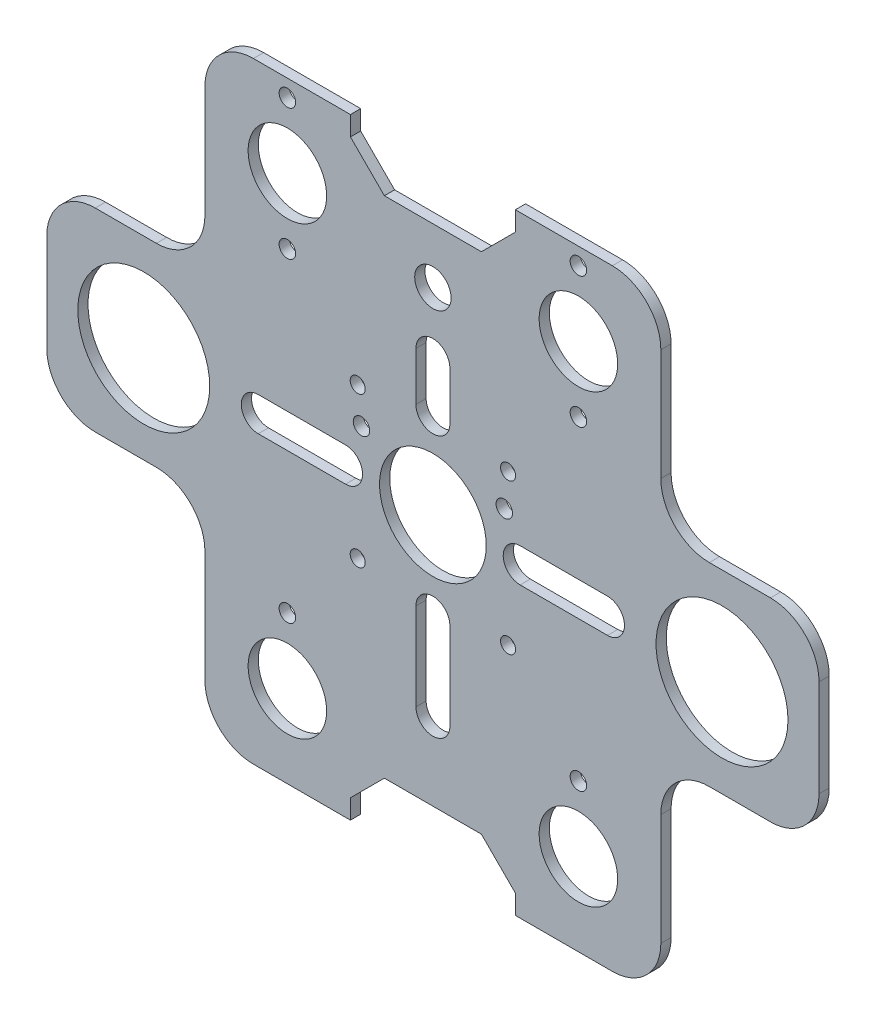
SolidWorks part; units mm, degrees
ref_plane "Alzado" through (0, 0, 0) normal (0, 0, 1) x (1, 0, 0)
ref_plane "Planta" through (0, 0, 0) normal (0, 1, 0) x (1, 0, 0)
ref_plane "Vista lateral" through (0, 0, 0) normal (1, 0, 0) x (0, 0, -1)
sketch "Croquis1" plane through (0, 0, 0) normal (0, 0, 1) x (1, 0, 0)
  line L0 (-79.61, 46) -> (79.61, 46)
  line L1 (-79.61, -46) -> (79.61, -46)
  line L2 (-79.61, -46) -> (-79.61, 46)
  line L4 (79.61, -46) -> (79.61, 46)
  line L5 (-79.61, -46) -> (79.61, 46) construction
  line L6 (-79.61, 46) -> (79.61, -46) construction
  point P0 (0, 0)
  point P8 (0, 45)
  point P10 (11.65, 45)
  dimension "D1" = 92
  dimension "D2" = 159.22
extrude "Saliente-Extruir1" add sketch "Croquis1" along normal blind 2.11
sketch "Croquis2" plane through (0, 0, 2.11) normal (0, 0, 1) x (1, 0, 0)
  line L0 (-79.61, 0) -> (79.61, 0) construction
  line L1 (-79.61, 46) -> (-79.61, -46) construction
  line L2 (79.61, -46) -> (79.61, 46) construction
  line L3 (0, -46) -> (0, 45) construction
  line L4 (-79.61, -46) -> (79.61, -46) construction
  circle A0 centre (59.61, 0) radius 13.6
  circle A1 centre (-59.61, 0) radius 13.6
  dimension "D1" = 27.2
  dimension "D2" = 20
extrude "Cortar-Extruir1" cut sketch "Croquis2" against normal up to surface (2.11 mm away) up to face at (0, 0, 0)
sketch "Croquis3" plane through (0, 0, 2.11) normal (0, 0, 1) x (1, 0, 0)
  line L0 (0, 0) -> (-78.1353, 0) construction
  line L1 (-15.5, -15.5) -> (15.5, -15.5) construction
  line L2 (-15.5, -15.5) -> (-15.5, 15.5) construction
  line L3 (-15.5, 15.5) -> (15.5, 15.5) construction
  line L4 (15.5, -15.5) -> (15.5, 15.5) construction
  line L5 (-15.5, -15.5) -> (15.5, 15.5) construction
  line L6 (-15.5, 15.5) -> (15.5, -15.5) construction
  line L7 (0, -46) -> (0, 45) construction
  line L8 (-79.61, -46) -> (79.61, -46) construction
  circle A0 centre (0, 0) radius 11
  circle A2 centre (15.5, 15.5) radius 1.55
  circle A4 centre (15.5, -15.5) radius 1.55
  circle A5 centre (-15.5, -15.5) radius 1.55
  circle A6 centre (-15.5, 15.5) radius 1.55
  point P19 (0, 0)
  dimension "D1" = 22
  dimension "D5" = 3.1
  dimension "D3" = 31
  dimension "D4" = 31
  dimension "D6" = 4
extrude "Cortar-Extruir2" cut sketch "Croquis3" against normal up to surface (2.11 mm away) up to face at (46.01, 0, 0)
sketch "Croquis4" plane through (0, 0, 0) normal (0, 0, -1) x (-1, 0, 0)
  line L0 (0, 0) -> (0, 27.7564) construction
  line L1 (-79.61, 20) -> (-30, 20)
  line L2 (-79.61, -46) -> (-79.61, 46) construction
  line L3 (-30, 20) -> (-30, 46)
  line L4 (-79.61, 46) -> (79.61, 46) construction
  line L5 (-79.61, 20) -> (-79.61, 46)
  line L6 (0, 0) -> (-26.4656, 0) construction
  line L7 (-79.61, 46) -> (-30, 46)
  line L8 (-30, -20) -> (-30, -46)
  line L9 (-79.61, -20) -> (-30, -20)
  line L10 (-79.61, -20) -> (-79.61, -46)
  line L11 (-79.61, -46) -> (-30, -46)
  line L12 (79.61, -46) -> (30, -46)
  line L13 (79.61, -20) -> (79.61, -46)
  line L14 (79.61, -20) -> (30, -20)
  line L15 (30, -20) -> (30, -46)
  line L16 (79.61, 46) -> (30, 46)
  line L17 (79.61, 20) -> (79.61, 46)
  line L18 (30, 20) -> (30, 46)
  line L19 (79.61, 20) -> (30, 20)
  dimension "D1" = 40
  dimension "D2" = 60
extrude "Cortar-Extruir3" cut sketch "Croquis4" against normal up to surface (2.11 mm away) up to face at (-13.95, 15.5, 2.11)
sketch "Croquis6" plane through (0, 0, 0) normal (0, 0, -1) x (-1, 0, 0)
  line L0 (0, 0) -> (0, 30.9825) construction
  line L1 (-47, 20) -> (-30, 20)
  line L3 (30, 20) -> (79.61, 20) construction
  line L4 (-47, 20) -> (-47, 63)
  line L5 (-47, 63) -> (-17, 63)
  line L6 (-17, 63) -> (-17, 52)
  line L7 (-17, 52) -> (17, 52)
  line L8 (17, 52) -> (17, 63)
  line L9 (17, 63) -> (47, 63)
  line L10 (47, 63) -> (47, 20)
  line L11 (47, 20) -> (30, 20)
  line L12 (0, 0) -> (24.021, 0) construction
  line L13 (30, 46) -> (30, 20)
  line L14 (-30, 20) -> (-30, 46)
  line L15 (-30, 46) -> (30, 46)
  line L16 (-79.61, 20) -> (-30, 20) construction
  line L21 (-30, -46) -> (30, -46)
  line L22 (-30, -20) -> (-30, -46)
  line L23 (30, -46) -> (30, -20)
  line L24 (47, -20) -> (30, -20)
  line L25 (47, -63) -> (47, -20)
  line L26 (17, -63) -> (47, -63)
  line L27 (17, -52) -> (17, -63)
  line L28 (-17, -52) -> (17, -52)
  line L29 (-17, -63) -> (-17, -52)
  line L30 (-47, -63) -> (-17, -63)
  line L31 (-47, -20) -> (-47, -63)
  line L32 (-47, -20) -> (-30, -20)
  circle A1 centre (-30, 46) radius 6.55 construction
  circle A2 centre (30, 46) radius 6.55 construction
  point P22 (0, 52)
  dimension "D1" = 13.1
  dimension "D2" = 94
  dimension "D3" = 30
  dimension "D4" = 6
  dimension "D6" = 43
sketch "Croquis5" plane through (0, 0, 0) normal (0, 0, -1) x (-1, 0, 0)
  line L0 (0, -36) -> (0, -18) construction
  line L1 (0, 0) -> (0, -36) construction
  line L2 (-3.5, -36) -> (-3.5, -18)
  line L3 (3.5, -36) -> (3.5, -18)
  line L4 (0, 0) -> (-14.7139, 0) construction
  line L5 (-36, 0) -> (-18, 0) construction
  line L8 (-36, 3.5) -> (-18, 3.5)
  line L9 (-36, -3.5) -> (-18, -3.5)
  line L10 (0, 28) -> (0, 18) construction
  line L11 (3.5, 28) -> (3.5, 18)
  line L12 (-3.5, 28) -> (-3.5, 18)
  line L13 (36, 0) -> (18, 0) construction
  line L14 (36, -3.5) -> (18, -3.5)
  line L15 (36, 3.5) -> (18, 3.5)
  circle A2 centre (-30, 46) radius 8.1
  circle A3 centre (30, 46) radius 8.1
  arc A4 (-3.5, -36) -> (3.5, -36) centre (0, -36) ccw
  arc A5 (3.5, -18) -> (-3.5, -18) centre (0, -18) ccw
  arc A8 (-36, 3.5) -> (-36, -3.5) centre (-36, 0) ccw
  arc A9 (-18, -3.5) -> (-18, 3.5) centre (-18, 0) ccw
  arc A10 (3.5, 28) -> (-3.5, 28) centre (0, 28) ccw
  arc A11 (-3.5, 18) -> (3.5, 18) centre (0, 18) ccw
  arc A12 (36, -3.5) -> (36, 3.5) centre (36, 0) ccw
  arc A13 (18, 3.5) -> (18, -3.5) centre (18, 0) ccw
  circle A14 centre (30, -46) radius 8.1
  circle A15 centre (-30, -46) radius 8.1
  point P7 (0, -27)
  point P24 (-27, 0)
  point P31 (0, 23)
  point P38 (27, 0)
  point P44 (0, 0)
  dimension "D2" = 10
  dimension "D4" = 16.2
  dimension "D6" = 3.5
  dimension "D1" = 36
extrude "Saliente-Extruir2" add sketch "Croquis6" against normal up to surface (2.11 mm away) up to face at (-13.95, 15.5, 2.11)
fillet "Redondeo2" radius 10 12 edges at (-79.61, -20, 1.055) (-79.61, 20, 1.055) (79.61, 20, 1.055) (79.61, -20, 1.055) (-47, 20, 1.055) (47, 20, 1.055) (-47, 63, 1.055) (47, 63, 1.055) (-47, -20, 1.055) (-47, -63, 1.055) (47, -20, 1.055) (47, -63, 1.055)
extrude "Cortar-Extruir4" cut sketch "Croquis5" against normal up to surface (2.11 mm away) up to face at (0, 0, 2.11)
chamfer "Chaflán1" distance 7 angle 45 4 edges at (-17, 52, 1.055) (17, 52, 1.055) (-17, -52, 1.055) (17, -52, 1.055)
sketch "Croquis8" plane through (0, 0, 0) normal (0, 0, -1) x (-1, 0, 0)
  line L0 (0, 0) -> (-25.212, 14.5561) construction
  line L1 (0, 0) -> (7.0013, 0) construction
  circle A0 centre (0, 0) radius 15 construction
  circle A1 centre (0, 0) radius 17 construction
  circle A2 centre (-14.7224, 8.5) radius 1.7
  dimension "D1" = 30
  dimension "D3" = 3.4
  dimension "D4" = 30
  dimension "D2" = 2
extrude "Cortar-Extruir5" cut sketch "Croquis8" against normal up to surface (2.11 mm away) contours A2 up to face at (0, -27, 2.11)
pattern_circular "MatrizC1" count 3 every 120 about axis through (0, 0, 0) along (0, 0, 1) of "Cortar-Extruir5"
sketch "Croquis9" plane through (0, 0, 0) normal (0, 0, -1) x (-1, 0, 0)
  line L0 (-30, 46) -> (-30, 14.3812) construction
  line L1 (0, 0) -> (0, 61.9302) construction
  line L2 (0, 0) -> (-5.4318, 0) construction
  line L3 (-30, 46) -> (-25.8999, 46) construction
  circle A0 centre (-30, 32.5) radius 1.7
  circle A1 centre (-30, 46) radius 8.1 construction
  circle A2 centre (30, 32.5) radius 1.7
  circle A4 centre (-30, 59.5) radius 1.7
  circle A6 centre (30, -32.5) radius 1.7
  circle A7 centre (-30, -32.5) radius 1.7
  circle A8 centre (30, 59.5) radius 1.7
  dimension "D1" = 3.4
  dimension "D2" = 13.5
extrude "Cortar-Extruir6" cut sketch "Croquis9" against normal up to surface (2.11 mm away) up to face at (-16.4224, 8.5, 2.11)
sketch "Croquis10" plane through (0, 0, 0) normal (0, 0, -1) x (-1, 0, 0)
  circle A0 centre (0, 0) radius 37.1 construction
  circle A1 centre (0, 40.6) radius 3.5 construction
  circle A2 centre (0, 40.6) radius 3.75
  dimension "D1" = 74.2
  dimension "D2" = 7
  dimension "D3" = 7.5
extrude "Cortar-Extruir7" cut sketch "Croquis10" against normal up to surface (2.11 mm away) contours A2 up to face at (-31.7, 32.5, 2.11)
